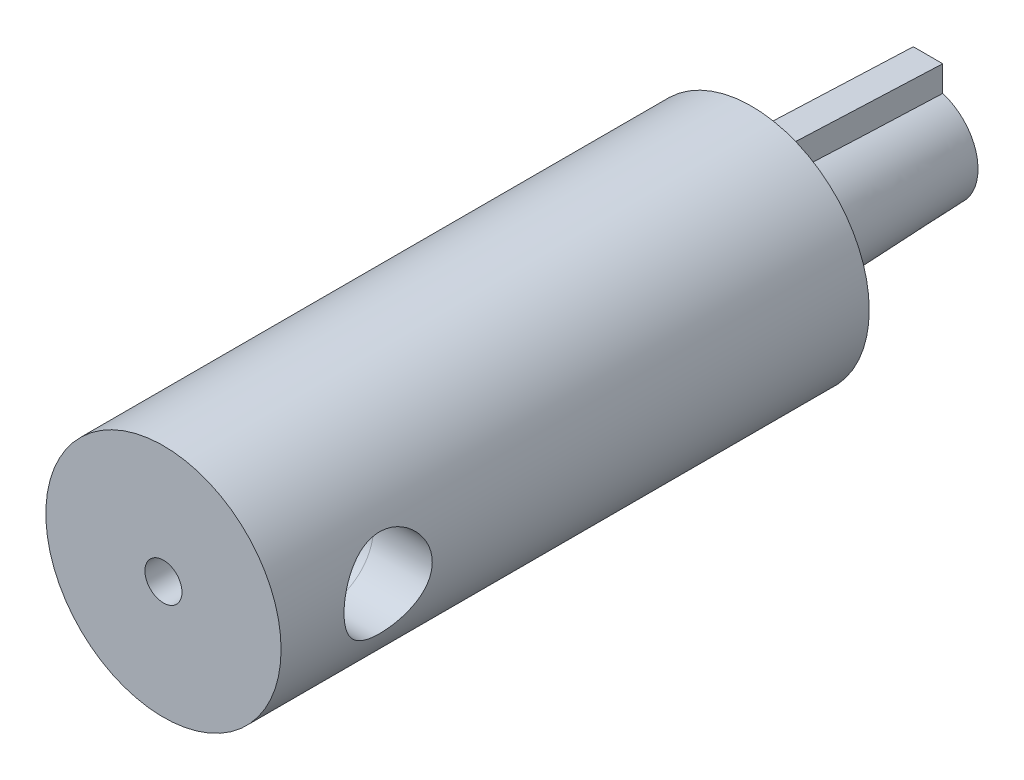
SolidWorks part; units mm, degrees
ref_plane "Front Plane" through (0, 0, 0) normal (0, 0, 1) x (1, 0, 0)
ref_plane "Top Plane" through (0, 0, 0) normal (0, 1, 0) x (1, 0, 0)
ref_plane "Right Plane" through (0, 0, 0) normal (1, 0, 0) x (0, 0, -1)
sketch "Sketch1" plane through (0, 0, 0) normal (0, 0, 1) x (1, 0, 0)
  circle A0 centre (0, 0) radius 20
  dimension "D1" = 40
extrude "Boss-Extrude1" add sketch "Sketch1" along normal blind 100
sketch "Sketch2" plane through (0, 0, 0) normal (0, 0, -1) x (-1, 0, 0)
  circle A0 centre (0, 0) radius 7.5
  dimension "D1" = 15
sketch "Sketch3" plane through (0, 0, 100) normal (0, 0, 1) x (1, 0, 0)
  circle A0 centre (0, 0) radius 3.15
  dimension "D1" = 6.3
extrude "Cut-Extrude2" cut sketch "Sketch3" against normal blind 5
sketch "Sketch4" plane through (0, 0, 0) normal (0, 1, 0) x (1, 0, 0)
  line L0 (0, 0) -> (0, -71.7939)
  line L1 (10, -81.7939) -> (20, -81.7939)
  line L3 (20, -100) -> (20, 0) construction
  arc A0 (0, -71.7939) -> (10, -81.7939) centre (10, -71.7939) ccw
  dimension "D1" = 10
sweep "Cut-Sweep1" cut profiles "Sketch2" path "Sketch4"
sketch "Sketch5" plane through (0, 0, 0) normal (0, 0, -1) x (-1, 0, 0)
  circle A0 centre (0, 0) radius 9.75
  dimension "D1" = 19.5
ref_plane "Plane1" through (0, 0, -30) normal (0, 0, 1) x (1, 0, 0)
sketch "Sketch6" plane through (0, 0, -30) normal (0, 0, 1) x (1, 0, 0)
  circle A0 centre (0, 0) radius 8.5
  dimension "D1" = 17
loft "Loft1" add profiles "Sketch6", "Sketch5" connector at (3.3021, -7.8324, -30) connector at (5.6763, -7.9273, 0)
sketch "Sketch7" plane through (0, 0, -30) normal (0, 0, -1) x (-1, 0, 0)
  circle A0 centre (0, 0) radius 4
  dimension "D1" = 8
extrude "Cut-Extrude3" cut sketch "Sketch7" against normal blind 30 contours A0
sketch "Sketch8" plane through (0, 0, -30) normal (0, 0, 1) x (1, 0, 0)
  line L0 (0, 0.7875) -> (0, 0) construction
  line L1 (0, 0) -> (0, 15.5007) construction
  line L2 (0, 0) -> (-21.2128, -12.2472) construction
  dimension "D1" = 120
sketch "Sketch9" plane through (0, 0, -30) normal (0, 0, 1) x (1, 0, 0)
  line L0 (0, 0) -> (0, 15.5007) construction
  line L1 (2.5, 5.7642) -> (-2.5, 5.7642)
  line L2 (2.5, 5.7642) -> (2.5, 12.5)
  line L3 (2.5, 12.5) -> (-2.5, 12.5)
  line L4 (-2.5, 5.7642) -> (-2.5, 12.5)
  line L5 (0, 8.5) -> (23.3832, 8.5) construction
  line L6 (23.3832, 8.5) -> (-17.3304, 8.5) construction
  circle A0 centre (0, 0) radius 8.5 construction
  dimension "D1" = 2.5
  dimension "D2" = 5
  dimension "D3" = 4
sketch "Sketch12" plane through (0, 0, 0) normal (0, 0, -1) x (-1, 0, 0)
  line L0 (0, 0) -> (0, 23.8516) construction
  line L1 (0, 9.75) -> (-17.4625, 9.75) construction
  line L2 (-17.4625, 9.75) -> (17.4625, 9.75) construction
  line L3 (2.5, 5.7642) -> (2.5, 12.5) construction
  line L4 (-2.5, 13.75) -> (2.5, 13.75)
  line L5 (-2.5, 13.75) -> (-2.5, 6.7704)
  line L6 (-2.5, 6.7704) -> (2.5, 6.7704)
  line L7 (2.5, 13.75) -> (2.5, 6.7704)
  circle A0 centre (0, 0) radius 9.75 construction
  circle A1 centre (0, 0) radius 20 construction
  dimension "D1" = 4
  dimension "D2" = 2.5
  dimension "D3" = 5
loft "Loft2" add profiles "Sketch12", "Sketch9" connector at (2.5, 13.75, 0) connector at (2.5, 12.5, -30)
